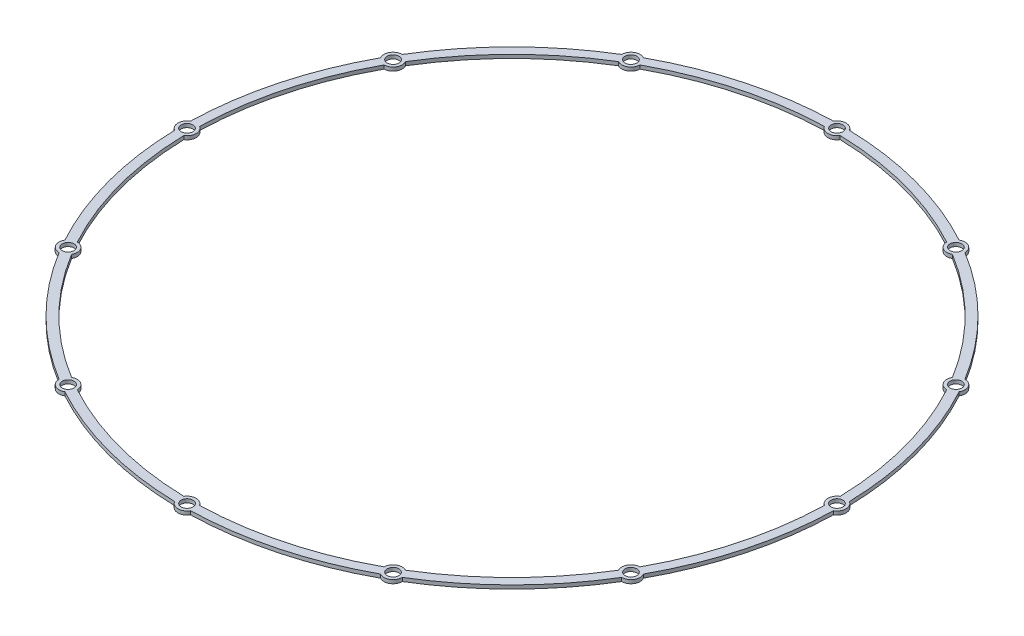
SolidWorks part; units mm, degrees
ref_plane "Front Plane" through (0, 0, 0) normal (0, 0, 1) x (1, 0, 0)
ref_plane "Top Plane" through (0, 0, 0) normal (0, 1, 0) x (1, 0, 0)
ref_plane "Right Plane" through (0, 0, 0) normal (1, 0, 0) x (0, 0, -1)
sketch "Sketch1" plane through (0, 0, 0) normal (0, 1, 0) x (1, 0, 0)
  circle A0 centre (0, 0) radius 90.805 construction
  circle A1 centre (0, 0) radius 92.075
  circle A2 centre (0, 0) radius 89.535
  circle A3 centre (0, 0) radius 93.345
  circle A4 centre (0, 0) radius 88.265
  circle A5 centre (0, -90.805) radius 1.651
  circle A6 centre (0, -90.805) radius 2.54
  dimension "D1" = 181.61
  dimension "D6" = 3.302
  dimension "D2" = 1.27
  dimension "D3" = 1.27
  dimension "D4" = 2.54
  dimension "D5" = 2.54
extrude "Boss-Extrude1" add sketch "Sketch1" along normal blind 1.016 contours A6 A1 A2 | A2 A6 A1 A5 | A1 A5 A2 | A1 A6 A2 A5 region at (65.6989, 0, 64.1371) region at (-1.9394, 0, 90.7869) region at (1.9394, 0, 90.7869) region at (0, 0, 90.8035)
extrude "Boss-Extrude2" add sketch "Sketch1<3>" along normal blind 1.016 contours A2 A6 A5 | A6 A1 A5 region at (0, 0, 92.6489) region at (0, 0, 88.9493)
sketch "Sketch1<3>" plane through (0, 0, 0) normal (0, 1, 0) x (1, 0, 0) same geometry as "Sketch1"
extrude "Cut-Extrude1" cut sketch "Sketch1<4>" along normal up to surface (1.016 mm away) contours A1 A5 | A2 A5 | A1 A5 A2 region at (0, 0, 90.8035) region at (0, 0, 92.2278) region at (0, 0, 89.3798) up to face at (0, 1.016, 0.635)
sketch "Sketch1<4>" plane through (0, 0, 0) normal (0, 1, 0) x (1, 0, 0) same geometry as "Sketch1"
pattern_circular "CirPattern2" count 12 over 360 about axis through (0, 1.016, 0) along (0, 1, 0) of "Cut-Extrude1", "Boss-Extrude2"
ref_plane "Plane1" through (0, 0.508, 0) normal (0, 1, 0) x (1, 0, 0)
sketch "Sketch2" plane through (0, 0.508, 0) normal (0, 1, 0) x (1, 0, 0)
  circle A0 centre (-78.6394, 45.4025) radius 1.651 construction
  circle A1 centre (-45.4025, 78.6394) radius 1.651 construction
  circle A2 centre (-90.805, 0) radius 1.651 construction
  circle A3 centre (-78.6394, -45.4025) radius 1.651 construction
  circle A4 centre (-45.4025, -78.6394) radius 1.651 construction
  circle A5 centre (0, -90.805) radius 1.651 construction
  circle A6 centre (45.4025, -78.6394) radius 1.651 construction
  circle A7 centre (78.6394, -45.4025) radius 1.651 construction
  circle A8 centre (90.805, 0) radius 1.651 construction
  circle A9 centre (78.6394, 45.4025) radius 1.651 construction
  circle A10 centre (45.4025, 78.6394) radius 1.651 construction
  circle A11 centre (0, 90.805) radius 1.651 construction
  circle A12 centre (-78.6394, 45.4025) radius 1.651
  circle A13 centre (-90.805, 0) radius 1.651
  circle A14 centre (-78.6394, -45.4025) radius 1.651
  circle A15 centre (-45.4025, -78.6394) radius 1.651
  circle A16 centre (0, -90.805) radius 1.651
  circle A17 centre (45.4025, -78.6394) radius 1.651
  circle A18 centre (78.6394, -45.4025) radius 1.651
  circle A19 centre (90.805, 0) radius 1.651
  circle A20 centre (78.6394, 45.4025) radius 1.651
  circle A21 centre (45.4025, 78.6394) radius 1.651
  circle A22 centre (0, 90.805) radius 1.651
  circle A23 centre (-45.4025, 78.6394) radius 1.651
  arc A24 (-47.9423, -78.6088) -> (-44.106, -80.8237) centre (-45.4025, -78.6394) ccw
  arc A25 (-44.106, -80.8237) -> (-2.2149, -92.0484) centre (0, 0) ccw
  arc A26 (-2.2149, -92.0484) -> (2.2149, -92.0484) centre (0, -90.805) ccw
  arc A27 (2.2149, -92.0484) -> (44.106, -80.8237) centre (0, 0) ccw
  arc A28 (44.106, -80.8237) -> (47.9423, -78.6088) centre (45.4025, -78.6394) ccw
  arc A29 (47.9423, -78.6088) -> (78.6088, -47.9423) centre (0, 0) ccw
  arc A30 (78.6088, -47.9423) -> (80.8237, -44.106) centre (78.6394, -45.4025) ccw
  arc A31 (80.8237, -44.106) -> (92.0484, -2.2149) centre (0, 0) ccw
  arc A32 (92.0484, -2.2149) -> (92.0484, 2.2149) centre (90.805, 0) ccw
  arc A33 (92.0484, 2.2149) -> (80.8237, 44.106) centre (0, 0) ccw
  arc A34 (80.8237, 44.106) -> (78.6088, 47.9423) centre (78.6394, 45.4025) ccw
  arc A35 (78.6088, 47.9423) -> (47.9423, 78.6088) centre (0, 0) ccw
  arc A36 (47.9423, 78.6088) -> (44.106, 80.8237) centre (45.4025, 78.6394) ccw
  arc A37 (44.106, 80.8237) -> (2.2149, 92.0484) centre (0, 0) ccw
  arc A38 (2.2149, 92.0484) -> (-2.2149, 92.0484) centre (0, 90.805) ccw
  arc A39 (-2.2149, 92.0484) -> (-44.106, 80.8237) centre (0, 0) ccw
  arc A40 (-44.106, 80.8237) -> (-47.9423, 78.6088) centre (-45.4025, 78.6394) ccw
  arc A41 (-47.9423, 78.6088) -> (-78.6088, 47.9423) centre (0, 0) ccw
  arc A42 (-78.6088, 47.9423) -> (-80.8237, 44.106) centre (-78.6394, 45.4025) ccw
  arc A43 (-80.8237, 44.106) -> (-92.0484, 2.2149) centre (0, 0) ccw
  arc A44 (-92.0484, 2.2149) -> (-92.0484, -2.2149) centre (-90.805, 0) ccw
  arc A45 (-92.0484, -2.2149) -> (-80.8237, -44.106) centre (0, 0) ccw
  arc A46 (-80.8237, -44.106) -> (-78.6088, -47.9423) centre (-78.6394, -45.4025) ccw
  arc A47 (-78.6088, -47.9423) -> (-47.9423, -78.6088) centre (0, 0) ccw
  arc A48 (-47.9423, -78.6088) -> (-44.106, -80.8237) centre (-45.4025, -78.6394) ccw
  arc A49 (-44.106, -80.8237) -> (-2.2149, -92.0484) centre (0, 0) ccw
  arc A50 (-2.2149, -92.0484) -> (2.2149, -92.0484) centre (0, -90.805) ccw
  arc A51 (2.2149, -92.0484) -> (44.106, -80.8237) centre (0, 0) ccw
  arc A52 (44.106, -80.8237) -> (47.9423, -78.6088) centre (45.4025, -78.6394) ccw
  arc A53 (47.9423, -78.6088) -> (78.6088, -47.9423) centre (0, 0) ccw
  arc A54 (78.6088, -47.9423) -> (80.8237, -44.106) centre (78.6394, -45.4025) ccw
  arc A55 (80.8237, -44.106) -> (92.0484, -2.2149) centre (0, 0) ccw
  arc A56 (92.0484, -2.2149) -> (92.0484, 2.2149) centre (90.805, 0) ccw
  arc A57 (92.0484, 2.2149) -> (80.8237, 44.106) centre (0, 0) ccw
  arc A58 (80.8237, 44.106) -> (78.6088, 47.9423) centre (78.6394, 45.4025) ccw
  arc A59 (78.6088, 47.9423) -> (47.9423, 78.6088) centre (0, 0) ccw
  arc A60 (47.9423, 78.6088) -> (44.106, 80.8237) centre (45.4025, 78.6394) ccw
  arc A61 (44.106, 80.8237) -> (2.2149, 92.0484) centre (0, 0) ccw
  arc A62 (2.2149, 92.0484) -> (-2.2149, 92.0484) centre (0, 90.805) ccw
  arc A63 (-2.2149, 92.0484) -> (-44.106, 80.8237) centre (0, 0) ccw
  arc A64 (-44.106, 80.8237) -> (-47.9423, 78.6088) centre (-45.4025, 78.6394) ccw
  arc A65 (-47.9423, 78.6088) -> (-78.6088, 47.9423) centre (0, 0) ccw
  arc A66 (-78.6088, 47.9423) -> (-80.8237, 44.106) centre (-78.6394, 45.4025) ccw
  arc A67 (-80.8237, 44.106) -> (-92.0484, 2.2149) centre (0, 0) ccw
  arc A68 (-92.0484, 2.2149) -> (-92.0484, -2.2149) centre (-90.805, 0) ccw
  arc A69 (-92.0484, -2.2149) -> (-80.8237, -44.106) centre (0, 0) ccw
  arc A70 (-80.8237, -44.106) -> (-78.6088, -47.9423) centre (-78.6394, -45.4025) ccw
  arc A71 (-78.6088, -47.9423) -> (-47.9423, -78.6088) centre (0, 0) ccw
  dimension "D1" = 0
equation "\"Middle Coupler Inner Daimeter\"= 6.25in"
equation "\"Middle Coupler  Wall Thickness\" = 0.25in"
equation "\"Middle Coupler Bottom Thickness\"= 0.2in"
equation "\"Bearing Rail Offset\"= 0.45in"
equation "\"3-56 UNF Tap\"= 0.089in"
equation "\"3-56 UNF Clearance\"= 0.104in"
equation "\"Ball Bearing Distance\"= 0.03in"
equation "\"TCA Outer Diameter\" = 8.625in"
equation "\"D1@Sketch1\"=\"Middle Coupler Inner Daimeter\"+\"Bearing Rail Offset\"*2in"
